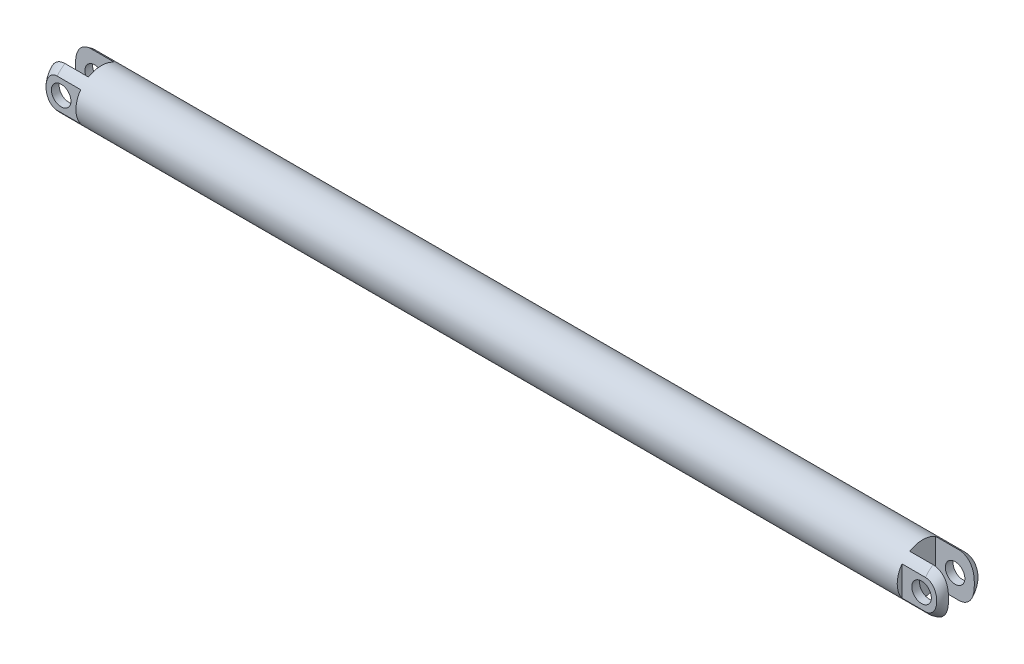
SolidWorks part; units mm, degrees
ref_plane "Front Plane" through (0, 0, 0) normal (1, 0, 0) x (0, 1, 0)
ref_plane "Top Plane" through (0, 0, 0) normal (0, 0, 1) x (0, 1, 0)
ref_plane "Right Plane" through (0, 0, 0) normal (0, 1, 0) x (-1, 0, 0)
sketch "Sketch1" plane through (0, 0, 0) normal (1, 0, 0) x (0, 1, 0)
  circle A0 centre (0, 0) radius 8.255
  dimension "D1" = 16.51
extrude "Boss-Extrude1" add sketch "Sketch1" against normal blind 266.7 contours A0
sketch "Sketch4" plane through (0, 0, 0) normal (1, 0, 0) x (0, 1, 0)
  line L0 (0, 0) -> (11.2668, 0) construction
  line L1 (-7.1139, -4.1878) -> (7.1139, -4.1878)
  line L2 (-7.1139, 4.1878) -> (7.1139, 4.1878)
  line L4 (-4.8215, 6.7006) -> (4.8215, 6.7006)
  line L6 (-4.8215, -6.7006) -> (4.8215, -6.7006)
  circle A0 centre (0, 0) radius 8.255 construction
  arc A1 (-4.8215, 6.7006) -> (-7.1139, 4.1878) centre (0, 0) ccw
  arc A2 (-7.1139, -4.1878) -> (-4.8215, -6.7006) centre (0, 0) ccw
  arc A3 (7.1139, 4.1878) -> (4.8215, 6.7006) centre (0, 0) ccw
  arc A4 (4.8215, -6.7006) -> (7.1139, -4.1878) centre (0, 0) ccw
extrude "Boss-Extrude2" add sketch "Sketch4" along normal blind 12.7
sketch "Sketch5" plane through (0, 0, 6.7006) normal (0, 0, 1) x (1, 0, 0)
  line L1 (0, 4.8215) -> (12.7, 4.8215) construction
  line L2 (0, 4.8215) -> (0, -4.8215) construction
  line L3 (0, -4.8215) -> (12.7, -4.8215) construction
  line L4 (12.7, 4.8215) -> (12.7, -4.8215) construction
  circle A0 centre (6.35, 0) radius 3.175
  dimension "D1" = 6.35
extrude "Cut-Extrude1" cut sketch "Sketch5" against normal through all contours A0
fillet "Fillet2" radius 5.08 2 edges at (12.7, 6.0985, -5.5635) (12.7, 6.0985, 5.5635)
ref_plane "Plane1" through (-133.35, 0, 0) normal (1, 0, 0) x (0, 0, -1)
mirror "Mirror1" about plane through (-133.35, 0, 0) normal (1, 0, 0) of "Fillet2", "Boss-Extrude2", "Boss-Extrude1", "Cut-Extrude1"
